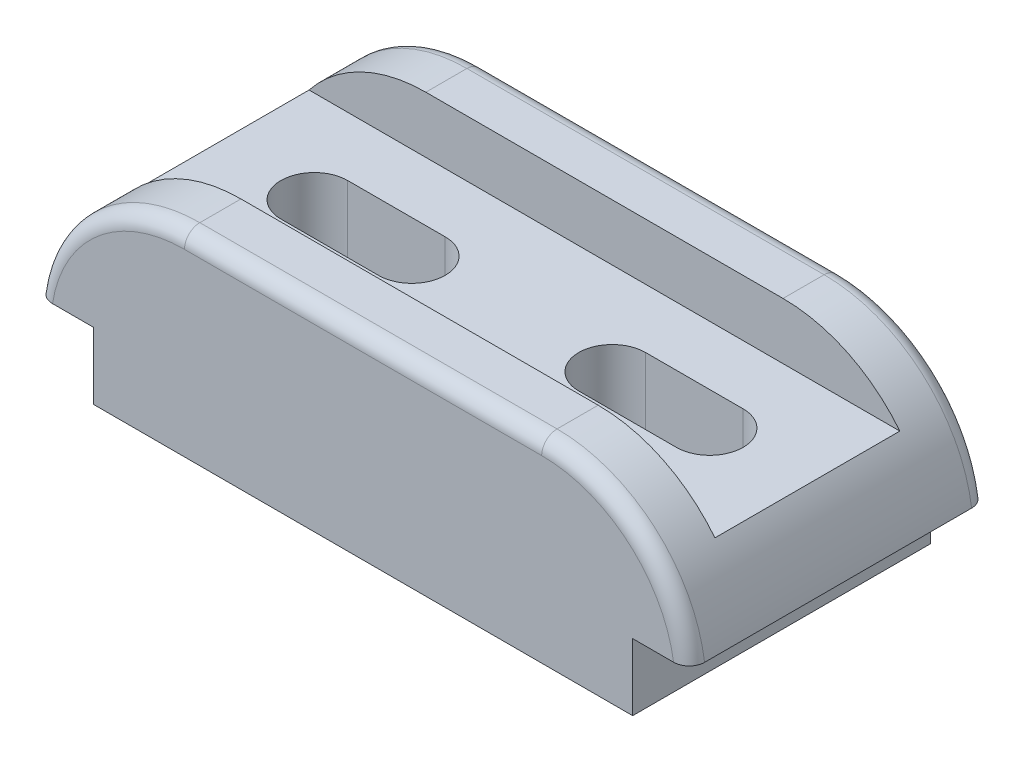
SolidWorks part; units mm, degrees
material "Laiton"
ref_plane "Face" through (0, 0, 0) normal (0, 0, 1) x (1, 0, 0)
ref_plane "Dessus" through (0, 0, 0) normal (0, 1, 0) x (1, 0, 0)
ref_plane "Droite" through (0, 0, 0) normal (1, 0, 0) x (0, 0, -1)
sketch "Esquisse1" plane through (0, 0, 0) normal (0, 0, 1) x (1, 0, 0)
  line L1 (-63.5, 0) -> (63.5, 0)
  line L2 (-63.5, 0) -> (-63.5, 38)
  line L3 (-63.5, 38) -> (63.5, 38)
  line L4 (63.5, 0) -> (63.5, 38)
  dimension "D1" = 127
  dimension "D2" = 38
extrude "Base-Extrusion" add sketch "Esquisse1" along normal mid plane 58
sketch "Esquisse2" plane through (0, 0, 29) normal (0, 0, 1) x (1, 0, 0)
  line L0 (-63.5, 38) -> (-63.5, 0) construction
  line L1 (-63.5, 13) -> (-52.5, 13)
  line L2 (-63.5, 13) -> (-63.5, 0)
  line L3 (-63.5, 0) -> (-52.5, 0)
  line L4 (-52.5, 13) -> (-52.5, 0)
  line L5 (-63.5, 0) -> (63.5, 0) construction
  line L6 (63.5, 0) -> (63.5, 38) construction
  line L7 (52.5, 0) -> (63.5, 0)
  line L8 (52.5, 0) -> (52.5, 13)
  line L9 (52.5, 13) -> (63.5, 13)
  line L10 (63.5, 0) -> (63.5, 13)
  dimension "D1" = 11
  dimension "D2" = 13
extrude "Enlèv. mat.-Extru.1" cut sketch "Esquisse2" against normal through all
fillet "Congé1" radius 29 2 edges at (63.5, 38, 0) (-63.5, 38, 0)
sketch "Esquisse3" plane through (0, 38, 0) normal (0, 1, 0) x (-1, 0, 0)
  line L0 (-63.5, -29) -> (-63.5, 29) construction
  line L1 (-63.5, -18) -> (63.5, -18)
  line L2 (-63.5, -18) -> (-63.5, 18)
  line L3 (-63.5, 18) -> (63.5, 18)
  line L4 (63.5, -18) -> (63.5, 18)
  line L5 (63.5, -29) -> (63.5, 29) construction
  line L6 (-63.5, -29) -> (-34.7772, -29) construction
  line L7 (-34.7772, 29) -> (-63.5, 29) construction
  dimension "D1" = 11
  dimension "D2" = 11
extrude "Enlèv. mat.-Extru.2" cut sketch "Esquisse3" against normal blind 11
sketch "Esquisse4" plane through (0, 27, 0) normal (0, 1, 0) x (-1, 0, 0)
  line L0 (19.5, -6.5) -> (38.5, -6.5)
  line L1 (19.5, 6.5) -> (38.5, 6.5)
  line L2 (-34.7772, 29) -> (34.7772, 29) construction
  line L3 (52.5, -29) -> (52.5, 29) construction
  arc A0 (38.5, 6.5) -> (38.5, -6.5) centre (38.5, 0) cw
  arc A1 (19.5, -6.5) -> (19.5, 6.5) centre (19.5, 0) cw
  dimension "D1" = 6.5
  dimension "D2" = 19
  dimension "D3" = 29
  dimension "D4" = 14
extrude "Enlèv. mat.-Extru.3" cut sketch "Esquisse4" against normal through all
mirror "Symétrie1" about plane through (0, 0, 0) normal (1, 0, 0) of "Enlèv. mat.-Extru.3"
fillet "Congé2" radius 3 6 edges at (53.8166, 30.8746, -29) (-53.8166, 30.8746, -29) (53.8166, 30.8746, 29) (-53.8166, 30.8746, 29) (0, 38, -29) (0, 38, 29)
